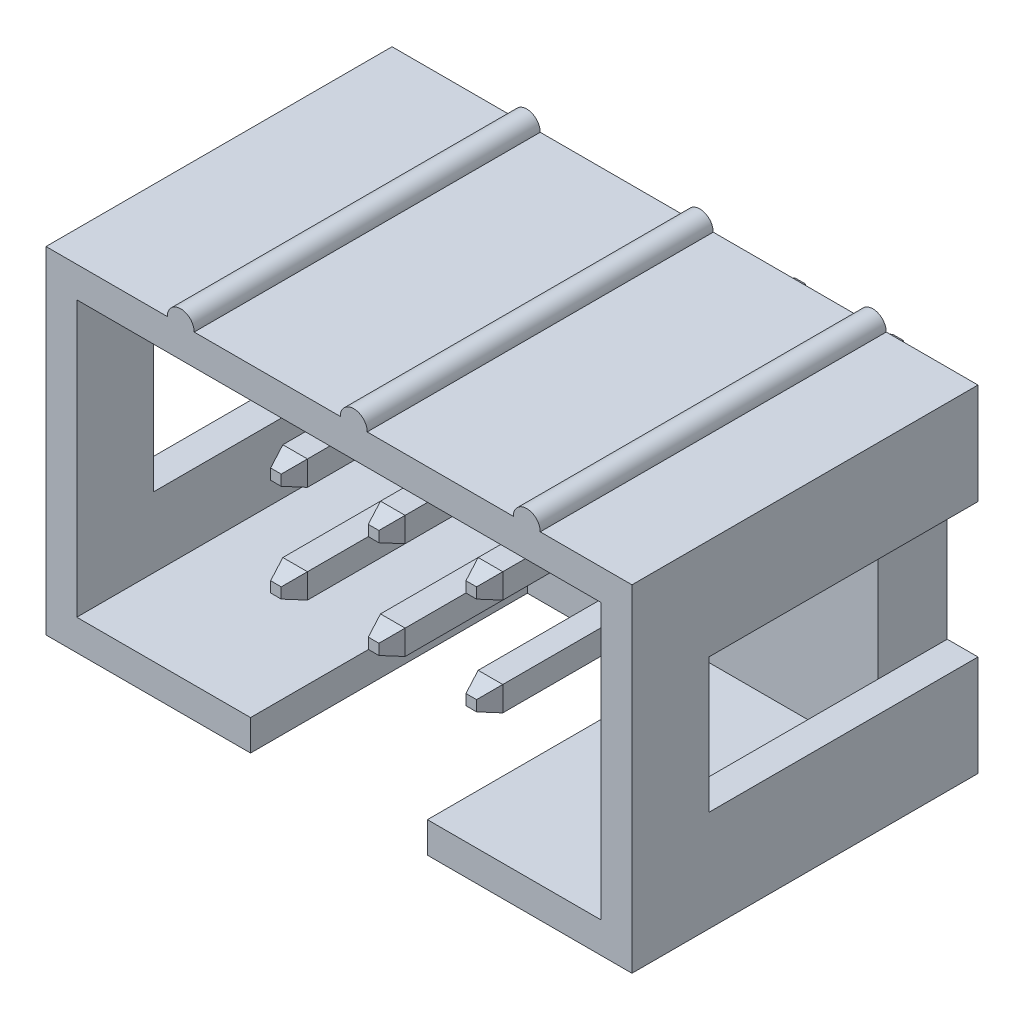
SolidWorks part; units mm, degrees
ref_plane "Спереди" through (0, 0, 0) normal (0, 0, 1) x (1, 0, 0)
ref_plane "Сверху" through (0, 0, 0) normal (0, 1, 0) x (1, 0, 0)
ref_plane "Справа" through (0, 0, 0) normal (1, 0, 0) x (0, 0, -1)
sketch "Эскиз1" plane through (0, 0, 0) normal (0, 0, 1) x (1, 0, 0)
  line L1 (-7.62, -4.375) -> (7.62, -4.375)
  line L2 (-7.62, -4.375) -> (-7.62, 4.375)
  line L3 (-7.62, 4.375) -> (7.62, 4.375)
  line L4 (7.62, -4.375) -> (7.62, 4.375)
  point P4 (0, 4.375)
  point P6 (-7.62, 0)
  dimension "D1" = 8.75
  dimension "D2" = 15.24
extrude "Бобышка-Вытянуть1" add sketch "Эскиз1" along normal blind 1.8
sketch "Эскиз2" plane through (0, 0, 1.8) normal (0, 0, 1) x (1, 0, 0)
  line L1 (-7.62, 4.375) -> (7.62, 4.375)
  line L2 (-7.62, 4.375) -> (-7.62, -4.375)
  line L3 (-7.62, -4.375) -> (7.62, -4.375)
  line L4 (7.62, 4.375) -> (7.62, -4.375)
  line L5 (-6.82, 3.575) -> (6.82, 3.575)
  line L6 (-6.82, 3.575) -> (-6.82, -3.575)
  line L7 (-6.82, -3.575) -> (6.82, -3.575)
  line L8 (6.82, 3.575) -> (6.82, -3.575)
  dimension "D1" = 0.8
  dimension "D2" = 0.8
  dimension "D3" = 0.8
  dimension "D4" = 0.8
extrude "Бобышка-Вытянуть2" add sketch "Эскиз2" along normal offset from surface (7.2 mm away) 9 up to face at (0, 0, 0)
sketch "Эскиз3" plane through (0, 0, 1.8) normal (0, 0, 1) x (1, 0, 0)
  line L0 (-7.62, 4.375) -> (-7.62, -4.375) construction
  line L1 (6.82, 1.75) -> (7.62, 1.75)
  line L2 (6.82, 1.75) -> (6.82, -1.75)
  line L3 (6.82, -1.75) -> (7.62, -1.75)
  line L4 (7.62, 1.75) -> (7.62, -1.75)
  line L5 (6.82, 1.75) -> (7.62, -1.75) construction
  line L6 (6.82, -1.75) -> (7.62, 1.75) construction
  line L7 (-6.82, 1.75) -> (-7.62, 1.75)
  line L8 (-6.82, 1.75) -> (-6.82, -1.75)
  line L9 (-6.82, -1.75) -> (-7.62, -1.75)
  line L10 (-7.62, 1.75) -> (-7.62, -1.75)
  line L11 (-6.82, 1.75) -> (-7.62, -1.75) construction
  line L12 (-6.82, -1.75) -> (-7.62, 1.75) construction
  line L13 (-6.82, 3.575) -> (-6.82, -3.575) construction
  line L14 (7.62, -4.375) -> (7.62, 4.375) construction
  line L16 (6.82, -3.575) -> (6.82, 3.575) construction
  point P0 (7.22, 0)
  point P5 (-7.22, 0)
  dimension "D1" = 3.5
extrude "Вырез-Вытянуть1" cut sketch "Эскиз3" against normal up to surface (1.8 mm away) and the other way offset from surface 2 up to face at (0, 0, 0) other way up to face at (0, 0, 9)
sketch "Эскиз4" plane through (0, 0, 9) normal (0, 0, 1) x (1, 0, 0)
  line L0 (6.82, -3.575) -> (-6.82, -3.575) construction
  line L1 (-2.3, -4.375) -> (2.3, -4.375)
  line L2 (-2.3, -4.375) -> (-2.3, -3.575)
  line L3 (-2.3, -3.575) -> (2.3, -3.575)
  line L4 (2.3, -4.375) -> (2.3, -3.575)
  line L5 (-2.3, -4.375) -> (2.3, -3.575) construction
  line L6 (-2.3, -3.575) -> (2.3, -4.375) construction
  line L7 (7.62, -4.375) -> (-7.62, -4.375) construction
  point P0 (0, -3.975)
  point P9 (0, 0)
  dimension "D1" = 4.6
extrude "Вырез-Вытянуть2" cut sketch "Эскиз4" against normal up to surface (7.2 mm away) up to face at (0, 0, 1.8)
sketch "Эскиз5" plane through (0, 0, 1.8) normal (0, 0, 1) x (1, 0, 0)
  line L0 (-2.54, 1.27) -> (2.54, 1.27) construction
  line L1 (2.54, 1.27) -> (2.54, -1.27) construction
  line L2 (2.54, -1.27) -> (-2.54, -1.27) construction
  line L3 (-2.54, -1.27) -> (-2.54, 1.27) construction
  line L5 (0, -1.27) -> (0, 1.27) construction
  line L6 (-2.86, 0.95) -> (-2.22, 0.95)
  line L7 (-2.86, 0.95) -> (-2.86, 1.59)
  line L8 (-2.86, 1.59) -> (-2.22, 1.59)
  line L9 (-2.22, 0.95) -> (-2.22, 1.59)
  line L10 (-2.86, 0.95) -> (-2.22, 1.59) construction
  line L11 (-2.86, 1.59) -> (-2.22, 0.95) construction
  line L15 (-0.32, 0.95) -> (0.32, 0.95)
  line L16 (-0.32, 0.95) -> (-0.32, 1.59)
  line L21 (-0.32, 1.59) -> (0.32, 1.59)
  line L22 (0.32, 0.95) -> (0.32, 1.59)
  line L23 (2.22, 0.95) -> (2.86, 0.95)
  line L24 (2.22, 0.95) -> (2.22, 1.59)
  line L25 (2.22, 1.59) -> (2.86, 1.59)
  line L26 (2.86, 0.95) -> (2.86, 1.59)
  line L27 (-2.86, -1.59) -> (-2.22, -1.59)
  line L28 (-2.86, -1.59) -> (-2.86, -0.95)
  line L29 (-2.86, -0.95) -> (-2.22, -0.95)
  line L30 (-2.22, -1.59) -> (-2.22, -0.95)
  line L31 (-0.32, -1.59) -> (-0.32, -0.95)
  line L32 (-0.32, -1.59) -> (0.32, -1.59)
  line L33 (0.32, -1.59) -> (0.32, -0.95)
  line L34 (-0.32, -0.95) -> (0.32, -0.95)
  line L35 (2.22, -1.59) -> (2.22, -0.95)
  line L36 (2.22, -0.95) -> (2.86, -0.95)
  line L37 (2.86, -1.59) -> (2.86, -0.95)
  line L38 (2.22, -1.59) -> (2.86, -1.59)
  point P12 (-2.54, 1.27)
  dimension "D1" = 2.54
  dimension "D2" = 2.54
  dimension "D3" = 0.64
  dimension "D4" = 3
  dimension "D5" = 2
extrude "Бобышка-Вытянуть3" add sketch "Эскиз5" along normal offset from surface 0.9 and the other way offset from surface 12 separate body contours L15 L22 L21 L16 region at (0, 1.27, 1.8) up to face at (0, -1.325, 9) other way up to face at (0, -1.325, 9)
chamfer "Фаска2" distance 0.5 angle 20 4 edges at (0, 1.59, -3) (-0.32, 1.27, -3) (0, 0.95, -3) (0.32, 1.27, -3) first distance on face at (0, 1.59, 2.55) first distance on face at (-0.32, 1.27, 2.55) first distance on face at (0, 0.95, 2.55) first distance on face at (0.32, 1.27, 2.55)
chamfer "Фаска8" distance 0.5 angle 20 4 edges at (0, 0.95, 8.1) (-0.32, 1.27, 8.1) (0, 1.59, 8.1) (0.32, 1.27, 8.1) first distance on face at (0, 0.95, 2.8) first distance on face at (-0.32, 1.27, 2.8) first distance on face at (0, 1.59, 2.8) first distance on face at (0.32, 1.27, 2.8)
sketch "Эскиз6" plane through (0, -4.375, 0) normal (0, -1, 0) x (1, 0, 0)
  line L0 (-4.9764, 5.1897) -> (-3.1846, 5.1897)
  line L1 (-3.1846, 5.1897) -> (-4.0805, 3.7162)
  line L2 (-4.0805, 3.7162) -> (-4.9764, 5.1897)
extrude "Вырез-Вытянуть3" cut sketch "Эскиз6" against normal blind 0.1
pattern_linear "Линейный массив1" count 2 spacing 2.54 along (-1, 0, 0) count 2 spacing 2.54 along (0, -1, 0) of bodies 108
pattern_linear "Линейный массив2" count 2 spacing 2.54 along (1, 0, 0) of bodies 115 108
sketch "Эскиз7" plane through (0, -4.625, 9) normal (0, 0, -1) x (1, 0, 0)
  line L2 (-7.62, -9) -> (7.62, -9) construction
  line L5 (7.62, -0.25) -> (2.3, -0.25) construction
  circle A0 centre (0.384, -9) radius 0.35
  circle A1 centre (4.884, -9) radius 0.35
  circle A2 centre (-4.116, -9) radius 0.35
  point P10 (4.884, -9.35)
  dimension "D1" = 4.5
  dimension "D2" = 4.5
  dimension "D3" = 9.1
extrude "Бобышка-Вытянуть4" add sketch "Эскиз7" along normal up to surface (9 mm away) up to face at (0, 0, 0)
equation "\"D3@Эскиз2\"=\"D2@Эскиз2\""
equation "\"D2@Эскиз2\"=\"D1@Эскиз2\""
equation "\"D4@Эскиз2\"=\"D1@Эскиз2\""
equation "\"D2@Эскиз5\"=\"D1@Эскиз5\""
equation "\"D2@Эскиз7\"=\"D1@Эскиз7\""
